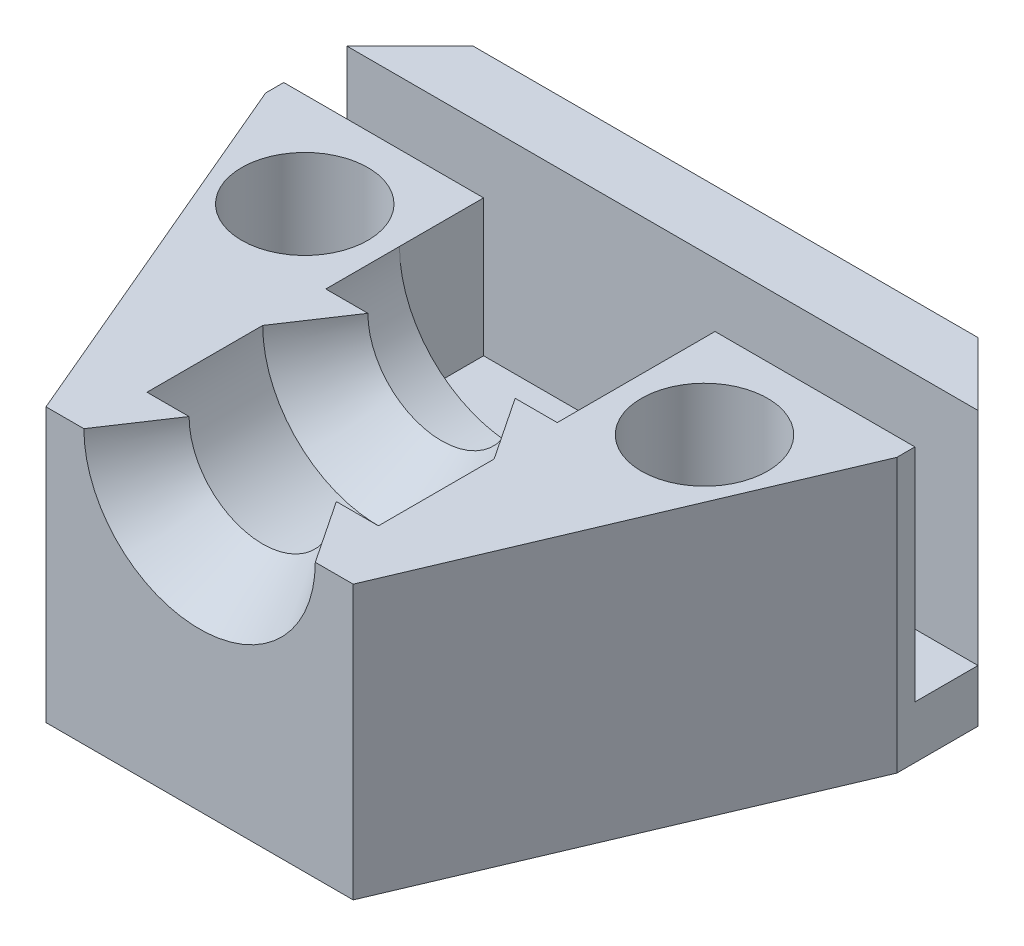
SolidWorks part; units mm, degrees
ref_plane "Front Plane" through (0, 0, 0) normal (0, 0, 1) x (1, 0, 0)
ref_plane "Top Plane" through (0, 0, 0) normal (0, 1, 0) x (1, 0, 0)
ref_plane "Right Plane" through (0, 0, 0) normal (1, 0, 0) x (0, 0, -1)
sketch "Sketch1" plane through (0, 0, 0) normal (0, 1, 0) x (1, 0, 0)
  line L1 (-7.5, 6.25) -> (7.5, 6.25)
  line L2 (-7.5, 6.25) -> (-7.5, -6.25)
  line L3 (-7.5, -6.25) -> (7.5, -6.25)
  line L4 (7.5, 6.25) -> (7.5, -6.25)
  line L5 (-7.5, 6.25) -> (7.5, -6.25) construction
  line L6 (-7.5, -6.25) -> (7.5, 6.25) construction
  point P0 (0, 0)
  dimension "D1" = 15
  dimension "D2" = 12.5
extrude "Boss-Extrude1" add sketch "Sketch1" along normal blind 6.5
sketch "Sketch2" plane through (0, 6.5, 0) normal (0, 1, 0) x (1, 0, 0)
  line L0 (7.5, -6.25) -> (7.5, 6.25) construction
  line L1 (-7.5, 6.25) -> (-7.5, -6.25) construction
  line L2 (7.5, 6.25) -> (-7.5, 6.25) construction
  circle A1 centre (4.75, 1) radius 1.5
  circle A2 centre (-4.75, 1) radius 1.5
  point P8 (0, 0)
  point P9 (0, 0)
  point P10 (0, 0)
  dimension "D1" = 3
  dimension "D2" = 3
  dimension "D3" = 2.75
  dimension "D4" = 2.75
  dimension "D5" = 5.25
extrude "Cut-Extrude1" cut sketch "Sketch2" against normal blind 5
sketch "Sketch3" plane through (0, 6.5, 0) normal (0, 1, 0) x (1, 0, 0)
  line L0 (-7.5, 4.75) -> (7.5, 4.75)
  line L1 (-7.5, 6.25) -> (-7.5, -6.25) construction
  line L2 (7.5, -6.25) -> (7.5, 6.25) construction
  line L3 (7.5, 4.75) -> (7.5, 3.25)
  line L4 (7.5, 3.25) -> (2.75, 3.25)
  line L5 (2.75, 3.25) -> (2.75, 1.25)
  line L6 (2.75, 1.25) -> (-2.75, 1.25)
  line L7 (-2.75, 1.25) -> (-2.75, 3.25)
  line L8 (-2.75, 3.25) -> (-7.5, 3.25)
  line L9 (-7.5, 3.25) -> (-7.5, 4.75)
  line L10 (7.5, 6.25) -> (-7.5, 6.25) construction
  line L11 (-2.75, 3.25) -> (2.75, 3.25)
  line M11 (7.5, -6.25) -> (7.5, 6.25)
  line M13 (-7.5, 6.25) -> (-7.5, -6.25)
  dimension "D1" = 5.5
  dimension "D2" = 2
  dimension "D3" = 1.5
  dimension "D4" = 1.5
extrude "Cut-Extrude4" cut sketch "Sketch3<3>" against normal blind 5.25 contours L8 L11 L4 L0 M11 M13 region at (0, 6.5, -4)
sketch "Sketch3<3>" plane through (0, 6.5, 0) normal (0, 1, 0) x (1, 0, 0) same geometry as "Sketch3"
sketch "Sketch4" plane through (0, 6.5, 0) normal (0, 1, 0) x (1, 0, 0)
  line L0 (2.75, 1.25) -> (2.75, -0.5)
  line L1 (2.75, -0.5) -> (1.75, -0.5)
  line L2 (1.75, -0.5) -> (2.75, -2)
  line L3 (2.75, -2) -> (2.75, -4.75)
  line L4 (2.75, -4.75) -> (1.75, -4.75)
  line L5 (1.75, -4.75) -> (2.75, -6.25)
  line L6 (-7.5, -6.25) -> (7.5, -6.25) construction
  line L7 (2.75, -6.25) -> (0, -6.25)
  line L11 (0, -6.25) -> (0, 1.25)
  line L12 (0, 1.25) -> (2.75, 1.25)
  dimension "D1" = 1
  dimension "D2" = 1.75
  dimension "D3" = 1.5
  dimension "D4" = 1.5
  dimension "D5" = 2.75
  dimension "D6" = 7.5
revolve "Cut-Revolve1" cut sketch "Sketch4" angle 360 about L11
chamfer "Chamfer1" distance 3.85 angle 67 2 edges at (-7.5, 3.25, 6.25) (7.5, 3.25, 6.25) first distance on face at (0, 3.875, 6.25)
extrude "Cut-Extrude3" cut sketch "Sketch3" against normal blind 3.25 contours L11 L7 L6 L5 region at (0, 6.5, -2.25)
chamfer "Chamfer2" distance 1.5 angle 45 2 edges at (-7.5, 3.25, -6.25) (7.5, 3.25, -6.25)
